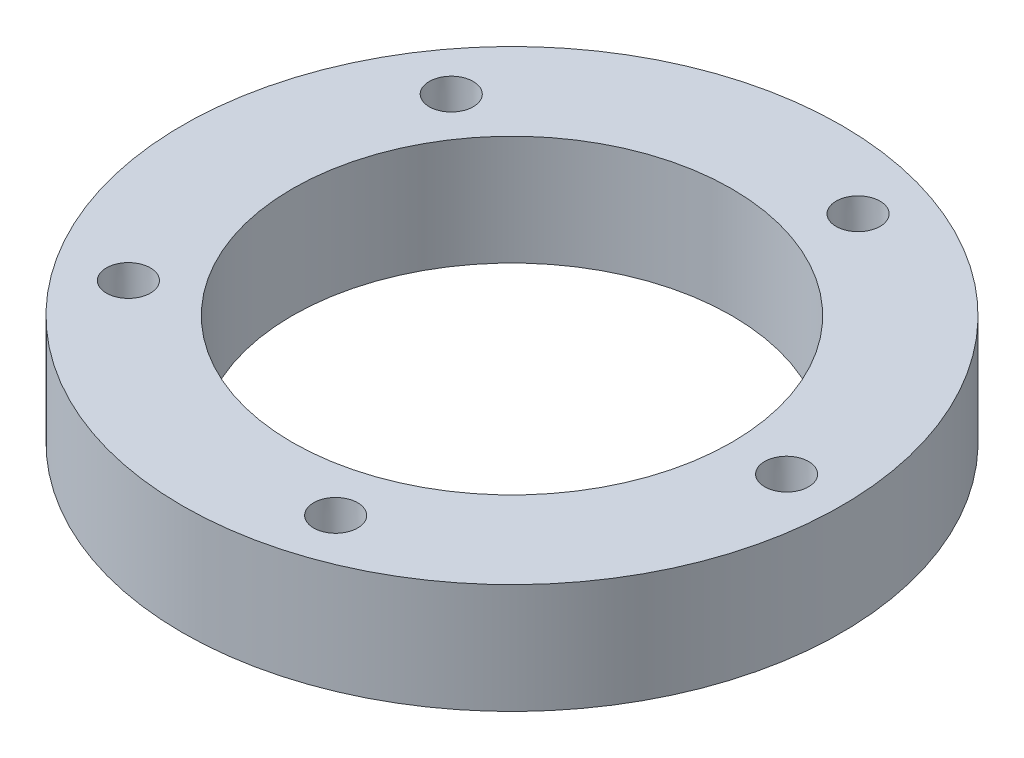
SolidWorks part; units mm, degrees
ref_plane "Front Plane" through (0, 0, 0) normal (0, 0, 1) x (1, 0, 0)
ref_plane "Top Plane" through (0, 0, 0) normal (0, 1, 0) x (1, 0, 0)
ref_plane "Right Plane" through (0, 0, 0) normal (1, 0, 0) x (0, 0, -1)
sketch "Sketch1" plane through (0, 0, 0) normal (0, 1, 0) x (1, 0, 0)
  circle A0 centre (0, 0) radius 10
  circle A1 centre (0, 0) radius 15
  dimension "D1" = 20
  dimension "D2" = 5
extrude "Boss-Extrude2" add sketch "Sketch1" along normal blind 5
sketch "Sketch2" plane through (0, 5, 0) normal (0, 1, 0) x (1, 0, 0)
  line L0 (-10, 0) -> (-15, 0) construction
  line L1 (-12.5, 0.9943) -> (-12.5, -1.1473) construction
  line L2 (0, 0) -> (11.5, 0) construction
  circle A0 centre (0, 0) radius 10 construction
  circle A1 centre (0, 0) radius 15 construction
  arc A2 (-10.6677, 6.5154) -> (-10.6677, -6.5154) centre (0, 0) ccw
  circle A3 centre (12.5, 0) radius 1
  circle A4 centre (3.8627, -11.8882) radius 1
  circle A5 centre (-10.1127, -7.3473) radius 1
  circle A6 centre (-10.1127, 7.3473) radius 1
  circle A7 centre (3.8627, 11.8882) radius 1
  arc A8 (2.9001, 12.1589) -> (-9.493, 8.1322) centre (0, 0) ccw
  arc A9 (12.46, 0.9992) -> (4.8006, 11.5414) centre (0, 0) ccw
  arc A10 (4.8006, -11.5414) -> (12.46, -0.9992) centre (0, 0) ccw
  arc A11 (-9.493, -8.1322) -> (2.9001, -12.1589) centre (0, 0) ccw
  dimension "D1" = 2
  dimension "D2" = 5
extrude "Cut-Extrude1" cut sketch "Sketch2" against normal blind 5 draft 2 contours A6 | A5 | A4 | A3 | A7 region at (-10.1127, 5, -7.3473) region at (-10.1127, 5, 7.3473) region at (3.8627, 5, -11.8882) region at (3.8627, 5, 11.8882) region at (12.5, 5, 0)
equation "\"outer-diameter\"= 20"
equation "\"screw-diameter\"= 2"
equation "\"bearing-thickness\"= 5"
